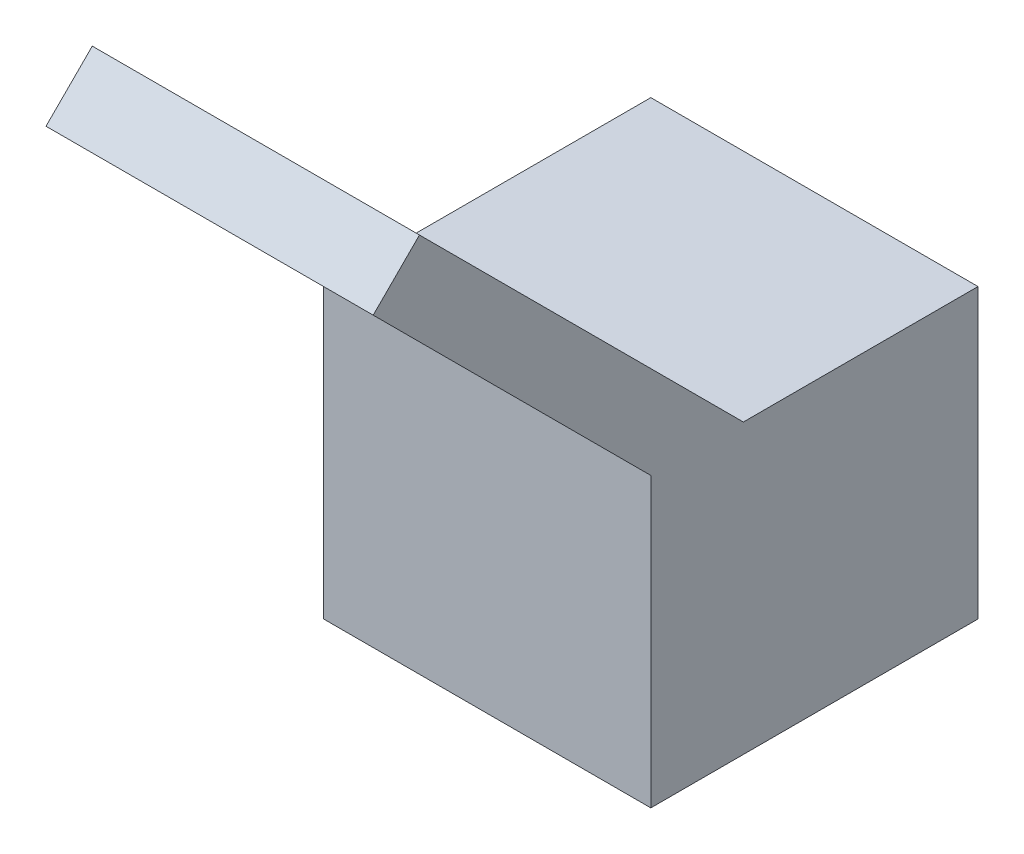
SolidWorks part; units mm, degrees
ref_plane "Front Plane" through (0, 0, 0) normal (0, 0, 1) x (1, 0, 0)
ref_plane "Top Plane" through (0, 0, 0) normal (0, 1, 0) x (1, 0, 0)
ref_plane "Right Plane" through (0, 0, 0) normal (1, 0, 0) x (0, 0, -1)
sketch "Sketch1" plane through (0, 0, 0) normal (0, 1, 0) x (1, 0, 0)
  line L0 (-12.5, -12.5) -> (-12.5, 12.5)
  line L1 (10.5, -10.5) -> (-10.5, -10.5)
  line L2 (10.5, -10.5) -> (10.5, 10.5)
  line L3 (10.5, 10.5) -> (-10.5, 10.5)
  line L4 (-10.5, -10.5) -> (-10.5, 10.5)
  line L5 (10.5, -10.5) -> (-10.5, 10.5) construction
  line L6 (10.5, 10.5) -> (-10.5, -10.5) construction
  line L7 (12.5, 12.5) -> (-12.5, 12.5)
  line L8 (12.5, -12.5) -> (12.5, 12.5)
  line L9 (12.5, -12.5) -> (-12.5, -12.5)
  point P0 (0, 0)
  dimension "D1" = 21
  dimension "D2" = 21
  dimension "D3" = 2
extrude "Boss-Extrude1" add sketch "Sketch1" against normal blind 2 contours L9 L8 L7 L0 L1 L4 L3 L2 | L4 L1 L2 L3 region at (-12.1464, 0, 0) region at (0, 0, 0)
extrude "Boss-Extrude2" add sketch "Sketch1<3>" against normal blind 20 from surface starting at face at (0, -2, 0)
sketch "Sketch1<3>" plane through (0, 0, 0) normal (0, 1, 0) x (1, 0, 0) same geometry as "Sketch1"
sketch "Sketch2" plane through (0, 0, -12.5) normal (0, 0, 1) x (1, 0, 0)
  line L0 (0, -22) -> (0, 0) construction
  line L7 (12.5, -22) -> (-12.5, -22) construction
  line L8 (12.5, 0) -> (-12.5, 0) construction
  circle A0 centre (0, -11) radius 1.75
  point P1 (0, -11)
  point P11 (0, 0)
  dimension "D1" = 3.5
extrude "Cut-Extrude1" cut sketch "Sketch2" along normal up to next
sketch "Sketch3" plane through (0, 0, 0) normal (1, 0, 0) x (0, 0, -1)
  line L0 (-12.5, 0) -> (-33.7132, 21.2132)
  line L1 (-33.7132, 21.2132) -> (-30.1777, 24.7487)
  line L2 (-30.1777, 24.7487) -> (-5.4289, 0)
  line L3 (-12.5, 0) -> (12.5, 0) construction
  line L4 (-5.4289, 0) -> (-12.5, 0)
  dimension "D1" = 30
  dimension "D2" = 135
  dimension "D3" = 5
extrude "Boss-Extrude3" add sketch "Sketch3" against normal through all from surface starting at face at (12.5, -11, 0)
sketch "Sketch4" plane through (0, -6.25, 6.25) normal (0, -0.7071, 0.7071) x (1, 0, 0)
  line L1 (12.5, 8.8388) -> (-12.5, 8.8388) construction
  line L2 (12.5, 8.8388) -> (12.5, 38.8388) construction
  line L3 (12.5, 38.8388) -> (-12.5, 38.8388) construction
  line L4 (-12.5, 8.8388) -> (-12.5, 38.8388) construction
  line L5 (12.5, 8.8388) -> (-12.5, 38.8388) construction
  line L6 (12.5, 38.8388) -> (-12.5, 8.8388) construction
  circle A0 centre (0, 23.8388) radius 3.3782
  point P0 (0, 23.8388)
  dimension "D1" = 6.7564
extrude "Cut-Extrude2" cut sketch "Sketch4" against normal through all
